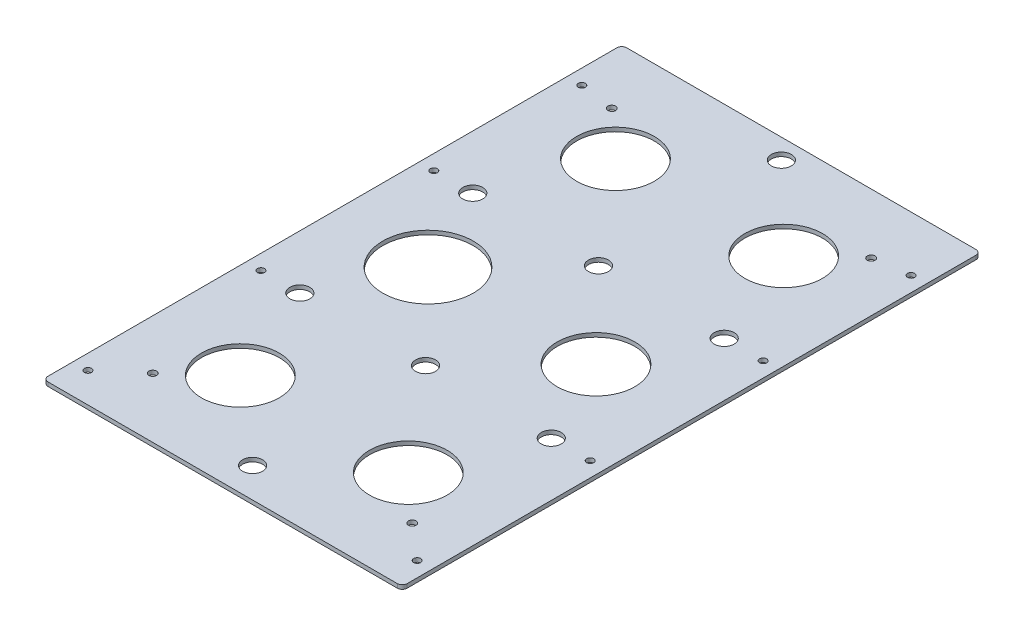
SolidWorks part; units mm, degrees
ref_plane "Front" through (0, 0, 0) normal (0, 0, 1) x (1, 0, 0)
ref_plane "Top" through (0, 0, 0) normal (0, 1, 0) x (1, 0, 0)
ref_plane "Right" through (0, 0, 0) normal (1, 0, 0) x (0, 0, -1)
sketch "Sketch1" plane through (0, 0, 0) normal (0, 1, 0) x (1, 0, 0)
  line L0 (-23.1141, -421.1347) -> (-23.2411, -421.1347) construction
  line L1 (-56.1213, -117.6047) -> (166.1287, -117.6047)
  line L2 (-59.2963, -120.7797) -> (-59.2963, -482.7297)
  line L3 (-56.1213, -485.9047) -> (166.1287, -485.9047)
  line L4 (169.3037, -120.7797) -> (169.3037, -482.7297)
  line L5 (-59.2963, -117.6047) -> (169.3037, -485.9047) construction
  line L6 (-59.2963, -485.9047) -> (169.3037, -117.6047) construction
  line L7 (-18.11, -281.6904) -> (21.0818, -321.6904) construction
  line L8 (81.9912, -485.9047) -> (166.1287, -485.9047) construction
  line L9 (169.3037, -482.7297) -> (169.3037, -120.7797) construction
  circle A0 centre (108.5215, -421.2633) radius 24.727
  circle A1 centre (108.5215, -301.819) radius 24.727
  circle A2 centre (1.4859, -421.1347) radius 24.727
  circle A4 centre (1.4859, -182.3747) radius 24.727
  circle A5 centre (108.5215, -182.3747) radius 24.727
  arc A6 (6.4427, -445.2302) -> (4.0942, -396.6734) centre (1.4859, -421.1347) ccw construction
  arc A7 (6.4427, -445.2302) -> (-3.4709, -397.0393) centre (1.4859, -421.1347) ccw construction
  arc A8 (169.3037, -120.7797) -> (166.1287, -117.6047) centre (166.1287, -120.7797) ccw
  arc A9 (-59.2963, -120.7797) -> (-56.1213, -117.6047) centre (-56.1213, -120.7797) cw
  arc A10 (-59.2963, -482.7297) -> (-56.1213, -485.9047) centre (-56.1213, -482.7297) ccw
  arc A11 (166.1287, -485.9047) -> (169.3037, -482.7297) centre (166.1287, -482.7297) ccw
  circle A12 centre (1.4859, -301.6904) radius 28.7693
  circle A13 centre (-25.0063, -356.7838) radius 2.2479 construction
  circle A14 centre (-25.0063, -356.7838) radius 2.2479 construction
  circle A15 centre (55.0037, -356.7881) radius 2.2479 construction
  circle A16 centre (55.0037, -356.7881) radius 2.2479 construction
  circle A17 centre (135.0137, -356.7838) radius 2.2479 construction
  circle A18 centre (135.0137, -356.7838) radius 2.2479 construction
  circle A19 centre (135.0137, -246.7256) radius 2.2479 construction
  circle A20 centre (135.0137, -246.7256) radius 2.2479 construction
  circle A21 centre (55.0037, -246.7214) radius 2.2479 construction
  circle A22 centre (55.0037, -246.7214) radius 2.2479 construction
  circle A23 centre (-25.0063, -246.7256) radius 2.2479 construction
  circle A24 centre (-25.0063, -246.7256) radius 2.2479 construction
  circle A25 centre (55.0037, -130.3047) radius 2.2479 construction
  circle A26 centre (55.0037, -130.3047) radius 2.2479 construction
  circle A27 centre (55.0037, -466.8547) radius 2.2479 construction
  circle A28 centre (55.0037, -466.8547) radius 2.2479 construction
  circle A29 centre (55.0037, -466.8547) radius 6.35
  circle A30 centre (135.0137, -356.7838) radius 6.35
  circle A31 centre (55.0037, -356.7881) radius 6.35
  circle A32 centre (-25.0063, -356.7838) radius 6.35
  circle A33 centre (135.0137, -246.7256) radius 6.35
  circle A34 centre (55.0037, -246.7214) radius 6.35
  circle A35 centre (-25.0063, -246.7256) radius 6.35
  circle A36 centre (55.0037, -130.3047) radius 6.35
  circle A37 centre (137.5537, -155.7047) radius 2.4574 construction
  circle A38 centre (137.5537, -155.7047) radius 2.4575
  circle A39 centre (-27.5463, -155.7047) radius 2.4575 construction
  circle A40 centre (-27.5463, -155.7047) radius 2.4575
  circle A41 centre (-27.5463, -447.8047) radius 2.4575 construction
  circle A42 centre (-27.5463, -447.8047) radius 2.4575
  circle A43 centre (137.5537, -447.8047) radius 2.4575 construction
  circle A44 centre (137.5537, -447.8047) radius 2.4575
  circle A45 centre (-49.7713, -152.5297) radius 2.2479 construction
  circle A46 centre (-49.7713, -152.5297) radius 2.2479
  circle A47 centre (-49.7713, -246.7214) radius 2.2479 construction
  circle A48 centre (-49.7713, -246.7214) radius 2.2479
  circle A49 centre (159.7787, -152.5297) radius 2.2479 construction
  circle A50 centre (159.7787, -152.5297) radius 2.2479
  circle A51 centre (159.7787, -246.7214) radius 2.2479 construction
  circle A52 centre (159.7787, -246.7214) radius 2.2479
  circle A53 centre (159.7787, -356.7881) radius 2.2479 construction
  circle A54 centre (159.7787, -356.7881) radius 2.2479
  circle A55 centre (-49.7713, -356.7881) radius 2.2479 construction
  circle A56 centre (-49.7713, -356.7881) radius 2.2479
  circle A57 centre (-49.7713, -466.8547) radius 2.2479 construction
  circle A58 centre (-49.7713, -466.8547) radius 2.2479
  circle A59 centre (159.7787, -466.8547) radius 2.2479 construction
  circle A60 centre (159.7787, -466.8547) radius 2.2479
  point P0 (55.0037, -301.7547)
  dimension "D3" = 0.127
  dimension "D4" = 3.175
  dimension "D5" = 12.7
  dimension "D1" = 228.6
  dimension "D2" = 368.3
extrude "Boss-Extrude1" add sketch "Sketch1" along normal blind 2.54
sketch "Sketch2" plane through (0, 2.54, 0) normal (0, 1, 0) x (1, 0, 0)
  line L0 (81.7963, -475.9047) -> (81.7963, -485.9047) construction
  line L2 (81.7963, -475.9047) -> (30.9963, -475.9047) construction
  line L3 (-56.1213, -485.9047) -> (166.1287, -485.9047) construction
  line L4 (169.3037, -482.7297) -> (169.3037, -120.7797) construction
  text T0 "WIRES OUT" font "Arial" height in points 26
  dimension "D1" = 10
  dimension "D2" = 50.8
  dimension "D3" = 87.5074
extrude "Cut-Extrude2" cut sketch "Sketch2" against normal blind 0.0254 rebuild error yes
